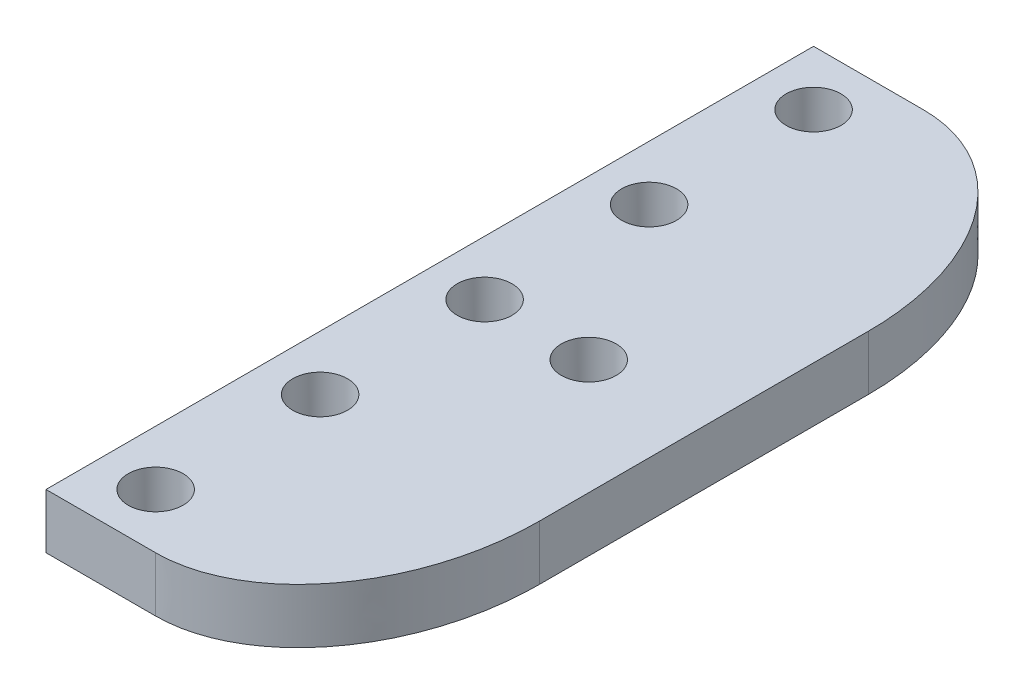
SolidWorks part; units mm, degrees
material "PLA"
ref_plane "Front Plane" through (0, 0, 0) normal (0, 0, 1) x (1, 0, 0)
ref_plane "Top Plane" through (0, 0, 0) normal (0, 1, 0) x (1, 0, 0)
ref_plane "Right Plane" through (0, 0, 0) normal (1, 0, 0) x (0, 0, -1)
sketch "Sketch1" plane through (0, 0, 0) normal (0, 0, 1) x (1, 0, 0)
  line L0 (6.5, 2.5) -> (12.5, 2.5)
  line L1 (-12.5, -2.5) -> (12.5, -2.5)
  line L2 (-12.5, -2.5) -> (-12.5, 2.5)
  line L3 (-12.5, 2.5) -> (6.5, 2.5)
  line L4 (12.5, -2.5) -> (12.5, 2.5)
  line L5 (-12.5, -2.5) -> (12.5, 2.5) construction
  line L6 (-12.5, 2.5) -> (12.5, -2.5) construction
  point P0 (0, 0)
  dimension "D1" = 25
  dimension "D2" = 5
extrude "Boss-Extrude1" add sketch "Sketch1" along normal blind 70
sketch "Sketch2" plane through (0, 2.5, 0) normal (0, 1, 0) x (1, 0, 0)
  line L0 (12.5, 0) -> (-12.5, 0) construction
  line L5 (12.5, -70) -> (-12.5, -70) construction
  line L11 (-12.5, -70) -> (-12.5, 0) construction
  line L24 (12.5, -70) -> (12.5, 0) construction
  line L32 (12.5, -70) -> (-12.5, -70) construction
  line L33 (-10.5, -35) -> (-1.5, -35) construction
  line L34 (12.5, 0) -> (-12.5, 0) construction
  circle A0 centre (-7.5, -5) radius 2.5
  circle A2 centre (-7.5, -20) radius 2.5
  circle A3 centre (-7.5, -35) radius 2.5
  circle A4 centre (-7.5, -50) radius 2.5
  circle A5 centre (-7.5, -65) radius 2.5
  circle A6 centre (2, -35) radius 2.5
  dimension "D7" = 10.5
  dimension "D3" = 5
  dimension "D6" = 5
  dimension "D1" = 5
  dimension "D2" = 5
  dimension "D4" = 5
  dimension "D5" = 5
extrude "Cut-Extrude2" cut sketch "Sketch2" against normal through all both and the other way through all contours A0 | A2 | A6 L33 | L33 A6 | A4 | A5 | A3 region at (-7.5, 2.5, 5) region at (-7.5, 2.5, 20) region at (-7.5, 2.5, 50) region at (-7.5, 2.5, 65) region at (2, 2.5, 35)
fillet "Fillet1" radius 15 2 edges at (12.5, 0, 70) (12.5, 0, 0) second distance 20 first distance on face at (0, 0, 70) first distance on face at (0, 0, 0)
